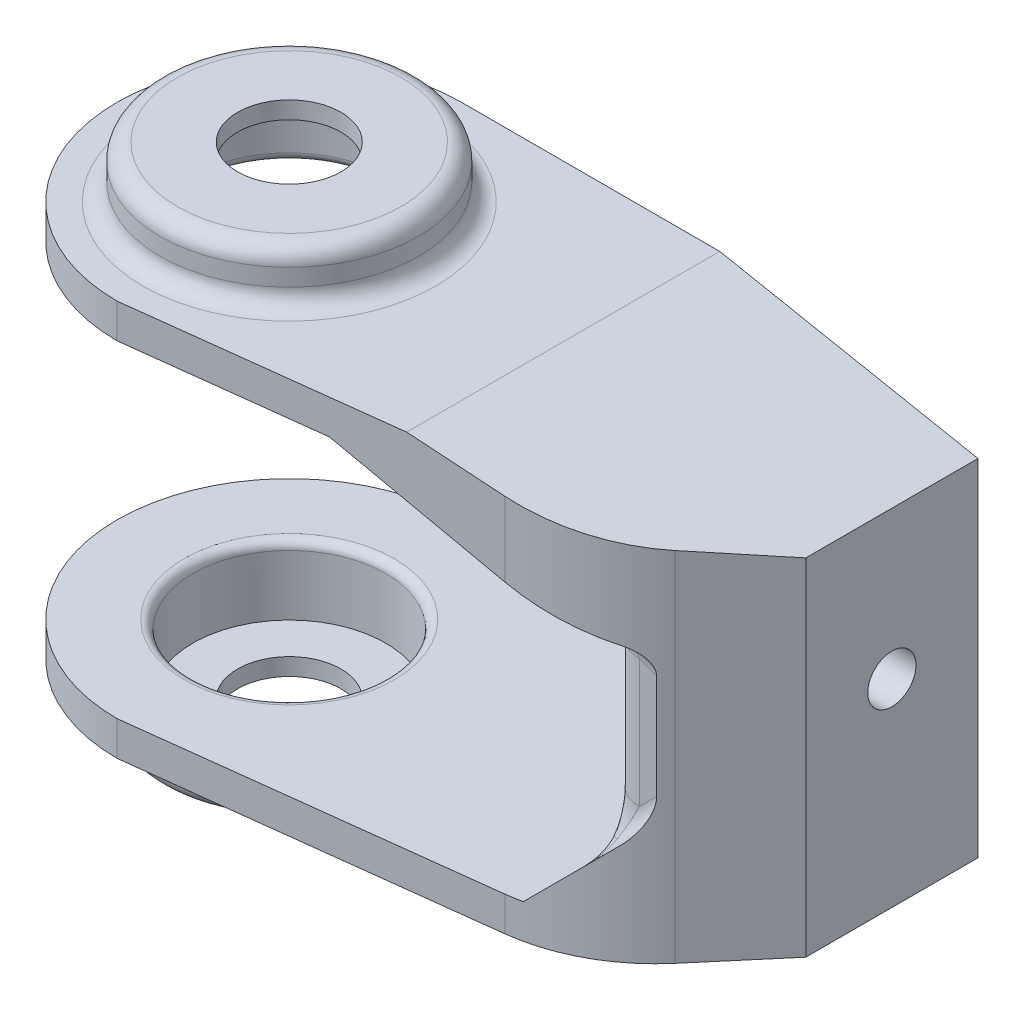
SolidWorks part; units mm, degrees
ref_plane "Front Plane" through (0, 0, 0) normal (0, 0, 1) x (1, 0, 0)
ref_plane "Top Plane" through (0, 0, 0) normal (0, 1, 0) x (1, 0, 0)
ref_plane "Right Plane" through (0, 0, 0) normal (1, 0, 0) x (0, 0, -1)
sketch "Sketch1" plane through (0, 0, 0) normal (0, 1, 0) x (1, 0, 0)
  line L1 (-20, 10) -> (20, 10)
  line L2 (-20, 10) -> (-20, -10)
  line L3 (-20, -10) -> (20, -10)
  line L4 (20, 10) -> (20, -10)
  line L5 (-20, 10) -> (20, -10) construction
  line L6 (-20, -10) -> (20, 10) construction
  point P0 (0, 0)
  dimension "D1" = 20
  dimension "D2" = 40
extrude "Boss-Extrude1" add sketch "Sketch1" along normal blind 23 contours L2 L4 region at (0, 0, 0)
sketch "Sketch2" plane through (-20, 0, 0) normal (-1, 0, 0) x (0, 0, 1)
  line L0 (-10, 11.5) -> (10, 11.5) construction
  line L3 (-10, 23) -> (-10, 0) construction
  line L4 (-16.3015, 21) -> (16.3015, 21)
  line L5 (-16.3015, 21) -> (-16.3015, 2)
  line L6 (-16.3015, 2) -> (16.3015, 2)
  line L7 (16.3015, 21) -> (16.3015, 2)
  line L8 (-16.3015, 21) -> (16.3015, 2) construction
  line L9 (-16.3015, 2) -> (16.3015, 21) construction
  line L10 (10, 23) -> (10, 0) construction
  point P6 (0, 11.5)
  dimension "D1" = 19
extrude "Cut-Extrude2" cut sketch "Sketch2" against normal blind 36
sketch "Sketch3" plane through (0, 23, 0) normal (0, 1, 0) x (1, 0, 0)
  line L0 (-20, 0) -> (20, 0) construction
  line L1 (-20, 10) -> (-20, -10) construction
  line L2 (20, 10) -> (20, -10) construction
  line L4 (20, 0) -> (20, 10)
  line L5 (20, 10) -> (-10, 10)
  line L6 (-10, -10) -> (10.0909, -7.5621)
  line L7 (-20, 10) -> (20, 10)
  line L8 (-20, 10) -> (-20, -10)
  line L9 (-20, -10) -> (20, -10)
  line L10 (20, 10) -> (20, -10)
  line L11 (16.5059, -4.1111) -> (20, 0)
  arc A0 (-10, 10) -> (-10, -10) centre (-10, 0) ccw
  circle A1 centre (-10, 0) radius 3
  arc A2 (10.0909, -7.5621) -> (16.5059, -4.1111) centre (8.8862, 2.3651) ccw
  line M2 (20, -10) -> (20, 10)
  line M3 (20, 10) -> (-20, 10)
  line M4 (-20, 10) -> (-20, -10)
  line M5 (-20, -10) -> (20, -10)
  dimension "D1" = 10
  dimension "D2" = 10
extrude "Cut-Extrude3" cut sketch "Sketch3" against normal blind 36 contours A0 M3 M4 | A0 L8 M5 | M5 M2 | L0 A1 | A1 L0 region at (-10, 23, 1.2732) region at (-10, 23, -1.2732) region at (12.1151, 23, 7.6423) region at (-17.7663, 23, 7.7663) region at (-17.7663, 23, -7.7663)
mirror "Mirror1" [suppressed]
sketch "Sketch4" plane through (0, 23, 0) normal (0, 1, 0) x (1, 0, 0)
  circle A0 centre (-10, 0) radius 7.5
extrude "Boss-Extrude2" add sketch "Sketch4" along normal blind 3
sketch "Sketch5" plane through (0, 21, 0) normal (0, -1, 0) x (1, 0, 0)
  circle A0 centre (-10, 0) radius 5.6
extrude "Cut-Extrude4" cut sketch "Sketch5" against normal blind 4
sketch "Sketch6" plane through (0, 0, 0) normal (0, -1, 0) x (1, 0, 0)
  circle A0 centre (-10, 0) radius 7.5
extrude "Boss-Extrude3" add sketch "Sketch6" along normal blind 3
sketch "Sketch7" plane through (0, 2, 0) normal (0, 1, 0) x (1, 0, 0)
  circle A0 centre (-10, 0) radius 5.6
extrude "Cut-Extrude5" cut sketch "Sketch7" against normal blind 4
sketch "Sketch8" plane through (0, 26, 0) normal (0, 1, 0) x (1, 0, 0)
  circle A0 centre (-10, 0) radius 3
extrude "Cut-Extrude6" cut sketch "Sketch8" against normal through all
fillet "Fillet1" radius 1 4 edges at (-10, 0, -7.5) (-10, -3, -7.5) (-10, 23, 7.5) (-10, 26, 7.5)
fillet "Fillet2" radius 0.5 2 edges at (-10, 21, -5.6) (-10, 2, 5.6)
chamfer "Chamfer1" distance 15 angle 20 1 edges at (16, 21, -2.6685) first distance on face at (-10, 21, 6.1)
chamfer "Chamfer2" distance 15 angle 11 1 edges at (20, 23, -5) first distance on face at (-10, 23, 8.5)
chamfer "Chamfer3" distance 5 angle 45 1 edges at (16, 2, -2.6685)
mirror "Mirror4" [suppressed]
sketch "Sketch9" [suppressed] plane through (0, 26, 0) normal (0, 1, 0) x (1, 0, 0)
  line L1 (20, 10) -> (-21.8584, 10)
  line L2 (20, 10) -> (20, -10.958)
  line L3 (20, -10.958) -> (-21.8584, -10.958)
  line L4 (-21.8584, 10) -> (-21.8584, -10.958)
extrude "Cut-Extrude7" [suppressed] cut sketch "Sketch9" against normal through all both and the other way through all
sketch "Sketch10" plane through (0, 0, 0) normal (0, -1, 0) x (1, 0, 0)
  circle A0 centre (8.8865, -5.17) radius 1.4
extrude "Cut-Extrude8" cut sketch "Sketch10" against normal blind 10
sketch "Sketch12" plane through (20, 0, 0) normal (1, 0, 0) x (0, 0, -1)
  line L0 (10, 0) -> (0, 0) construction
  line L1 (10, 20.0843) -> (7.5, 20.0843)
  line L2 (10, 20.0843) -> (10, 0)
  line L3 (10, 0) -> (7.5, 0)
  line L4 (7.5, 20.0843) -> (7.5, 0)
extrude "Boss-Extrude4" add sketch "Sketch12" against normal blind 13
fillet "Fillet3" radius 5 2 edges at (7, 2, -8.75) (7, 18.8162, -8.75)
fillet "Fillet4" radius 3 2 edges at (9.8551, 17.777, -7.5) (13.5, 4.5, -7.5)
sketch "Sketch13" plane through (16, 0, 0) normal (-1, 0, 0) x (0, 0, 1)
  line L0 (-10, 20.0136) -> (-10, 15.3151) construction
  line L1 (-10, 18.6023) -> (4.663, 18.6023)
  line L2 (-10, 18.6023) -> (-10, 1.3217)
  line L3 (-10, 1.3217) -> (4.663, 1.3217)
  line L4 (4.663, 18.6023) -> (4.663, 1.3217)
extrude "Boss-Extrude5" add sketch "Sketch13" along normal blind 3
sketch "Sketch11" plane through (20, 0, 0) normal (1, 0, 0) x (0, 0, -1)
  circle A0 centre (5, 11.5) radius 1.4
extrude "Cut-Extrude9" cut sketch "Sketch11" against normal blind 10
fillet "Fillet5" radius 1 7 edges at (13, 4, 0.0815) (13, 5.2426, -6.6213) (13, 10.8412, -7.5) (13, 15.6973, -6.6213) (14.5, 5.5, 4.663) (13, 16.6324, 0.0815) (14.5, 16.0864, 4.663)
fillet "Fillet6" radius 2 5 edges at (12.9239, 4.0315, 5.2803) (13, 4.873, 4.7391) (12.8192, 16.5057, 5.0894) (13, 15.753, 4.6782) (13, 10.4912, 4.663)
sketch "Sketch14" plane through (20, 0, 0) normal (1, 0, 0) x (0, 0, -1)
  line L0 (5, 10.1) -> (10, 10.0421)
  line L1 (10, 20.0843) -> (10, 0) construction
  circle A0 centre (5, 11.5) radius 1.4 construction
sketch "Sketch15" plane through (0, 0, -10) normal (0, 0, -1) x (-1, 0, 0)
  circle A0 centre (-9.5, 10.0421) radius 1.4
extrude "Cut-Extrude10" cut sketch "Sketch15" against normal blind 2.5 contours A0 region at (9.5, 10.0421, -10)
